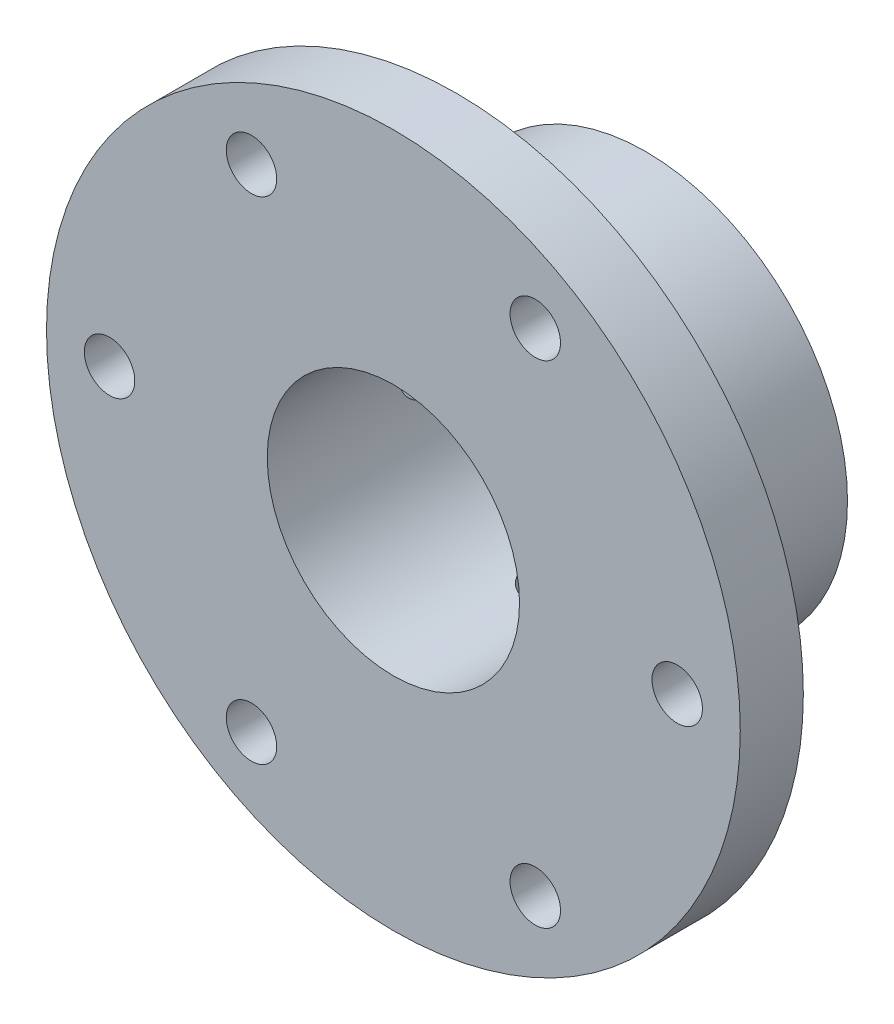
SolidWorks part; units mm, degrees
material "1060 Сплав"
ref_plane "Спереди" through (0, 0, 0) normal (0, 0, 1) x (1, 0, 0)
ref_plane "Сверху" through (0, 0, 0) normal (0, 1, 0) x (1, 0, 0)
ref_plane "Справа" through (0, 0, 0) normal (1, 0, 0) x (0, 0, -1)
sketch "Эскиз1" plane through (0, 0, 0) normal (0, 0, 1) x (1, 0, 0)
  circle A1 centre (0, 0) radius 27.5
  dimension "D2" = 55
extrude "Бобышка-Вытянуть1" add sketch "Эскиз1" along normal blind 5
sketch "Эскиз2" plane through (0, 0, 0) normal (0, 0, -1) x (-1, 0, 0)
  circle A0 centre (0, 0) radius 16
  circle A2 centre (0, 0) radius 10
  dimension "D1" = 32
  dimension "D2" = 20
extrude "Вырез-Вытянуть2" cut sketch "Эскиз2" against normal through all contours A2
extrude "Бобышка-Вытянуть9" add sketch "Эскиз2<12>" along normal blind 15
sketch "Эскиз2<12>" plane through (0, 0, 0) normal (0, 0, -1) x (-1, 0, 0) same geometry as "Эскиз2"
sketch "Эскиз12" plane through (0, 0, 0) normal (0, 0, -1) x (-1, 0, 0)
  line L0 (0, 0) -> (-22.5, 0) construction
  circle A0 centre (0, 0) radius 22.5 construction
  circle A1 centre (-22.5, 0) radius 2
  circle A2 centre (0, 0) radius 22.5 construction
  circle A3 centre (-11.25, 19.4856) radius 2
  circle A4 centre (0, 0) radius 22.5 construction
  circle A5 centre (11.25, 19.4856) radius 2
  circle A6 centre (0, 0) radius 22.5 construction
  circle A7 centre (22.5, 0) radius 2
  circle A8 centre (0, 0) radius 22.5 construction
  circle A9 centre (11.25, -19.4856) radius 2
  circle A10 centre (0, 0) radius 22.5 construction
  circle A11 centre (-11.25, -19.4856) radius 2
  dimension "D1" = 45
  dimension "D2" = 4
  dimension "D3" = 6
extrude "Вырез-Вытянуть3" cut sketch "Эскиз12" against normal through all contours A7 | A5 | A3 | A1 | A11 | A9
chamfer "Фаска1" distance 0.5 angle 45 6 edges at (-24.5, 0, 0) (-13.25, -19.4856, 0) (9.25, -19.4856, 0) (20.5, 0, 0) (-13.25, 19.4856, 0) (9.25, 19.4856, 0)
ref_plane "Плоскость1" through (0, 16, 0) normal (0, 1, 0) x (1, 0, 0)
sketch "Эскиз13" plane through (0, 16, 0) normal (0, 1, 0) x (1, 0, 0)
  line L0 (-16, 15) -> (-16, 0) construction
  line L1 (10, 15) -> (-10, 15) construction
  circle A0 centre (0, 7.5) radius 2
  dimension "D1" = 4
  dimension "D2" = 16
  dimension "D3" = 7.5
extrude "Вырез-Вытянуть4" cut sketch "Эскиз13" against normal up to next contours A0
pattern_circular "Круговой массив1" count 4 over 360 about axis through (0, 0, -15) along (0, 0, 1) of "Вырез-Вытянуть4"
